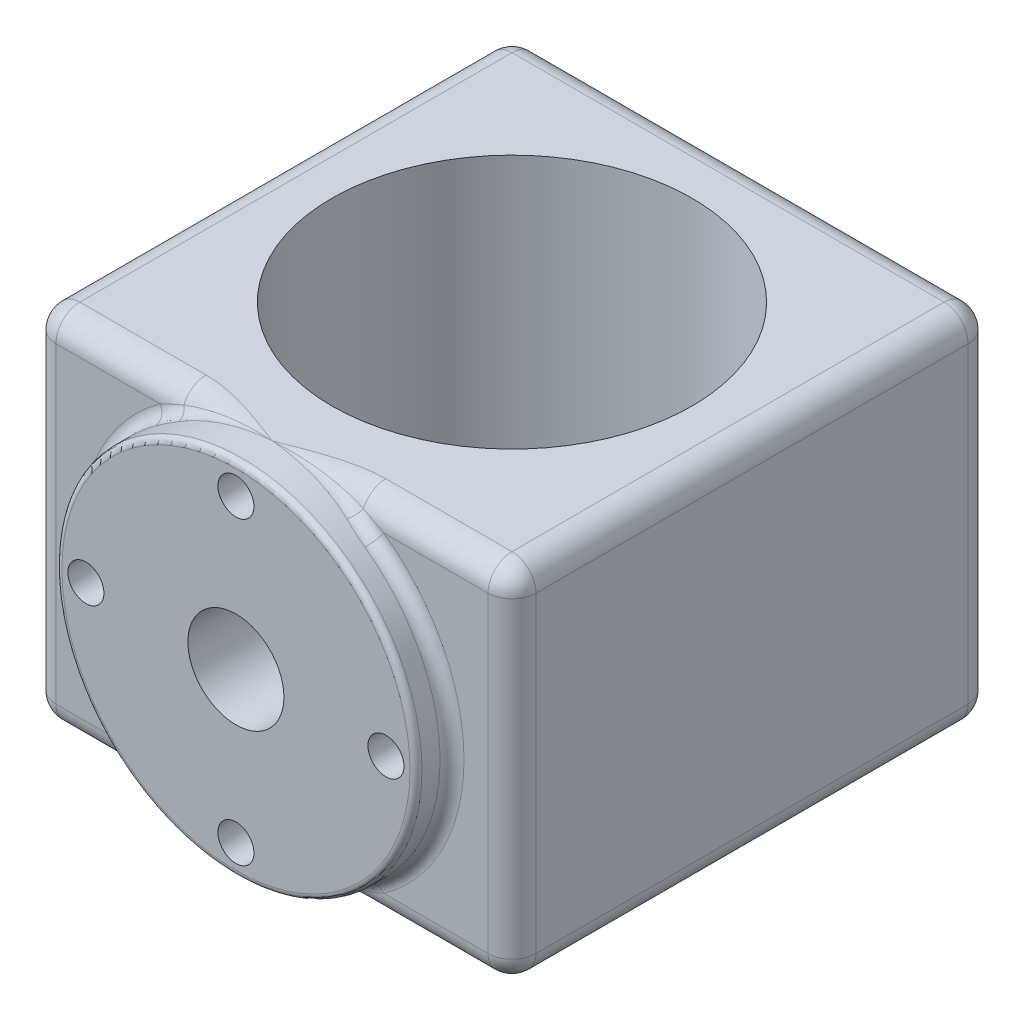
SolidWorks part; units mm, degrees
ref_plane "Front Plane" through (0, 0, 0) normal (0, 0, 1) x (1, 0, 0)
ref_plane "Top Plane" through (0, 0, 0) normal (0, 1, 0) x (1, 0, 0)
ref_plane "Right Plane" through (0, 0, 0) normal (1, 0, 0) x (0, 0, -1)
sketch "Sketch2" plane through (0, 0, 0) normal (0, 0, 1) x (1, 0, 0)
  line L2 (0, 0) -> (-12.5, 0) construction
  circle A0 centre (-12.5, 0) radius 1.5
  circle A5 centre (0, 0) radius 15
  circle A6 centre (0, 12.5) radius 1.5
  circle A7 centre (12.5, 0) radius 1.5
  circle A8 centre (0, -12.5) radius 1.5
  dimension "D1" = 30
  dimension "D2" = 3
  dimension "D3" = 12.5
  dimension "D4" = 4
extrude "Boss-Extrude1" add sketch "Sketch2" along normal blind 3
sketch "Sketch3" plane through (0, 0, 0) normal (0, 0, -1) x (-1, 0, 0)
  line L1 (-20, -15) -> (20, -15)
  line L2 (-20, -15) -> (-20, 15)
  line L3 (-20, 15) -> (20, 15)
  line L4 (20, -15) -> (20, 15)
  line L5 (-20, -15) -> (20, 15) construction
  line L6 (-20, 15) -> (20, -15) construction
  point P0 (0, 0)
  dimension "D1" = 30
  dimension "D2" = 40
extrude "Boss-Extrude2" add sketch "Sketch3" along normal blind 40
sketch "Sketch4" plane through (0, 15, 0) normal (0, 1, 0) x (1, 0, 0)
  line L0 (0, 0) -> (0, 40) construction
  line L1 (-20, 40) -> (20, 40) construction
  circle A0 centre (0, 20) radius 15
  dimension "D1" = 30
extrude "Cut-Extrude1" cut sketch "Sketch4" against normal up to surface (30 mm away) up to face at (0, -15, -16)
fillet "Fillet1" radius 2 14 edges at (-10, -15, 0) (-10, 15, 0) (-20, 0, 0) (20, 0, -40) (0, 15, -40) (-20, 0, -40) (-20, 15, -20) (-20, -15, -20) (0, -15, -40) (20, -15, -20) (10, -15, 0) (10, 15, 0) (20, 0, 0) (20, 15, -20)
fillet "Fillet2" radius 0.5 1 edges at (15, 0, 3)
fillet "Fillet3" radius 1 6 edges at (3.873, -14.4914, 0) (-3.873, -14.4914, 0) (-15, 0, 0) (-3.873, 14.4914, 0) (3.873, 14.4914, 0) (15, 0, 0)
sketch "Sketch5" plane through (0, 0, 3) normal (0, 0, 1) x (1, 0, 0)
  circle A0 centre (0, -12.5) radius 1.5 construction
  circle A1 centre (12.5, 0) radius 1.5 construction
  circle A2 centre (0, 12.5) radius 1.5 construction
  circle A3 centre (-12.5, 0) radius 1.5 construction
  circle A4 centre (0, -12.5) radius 1.5
  circle A5 centre (12.5, 0) radius 1.5
  circle A6 centre (0, 12.5) radius 1.5
  circle A7 centre (-12.5, 0) radius 1.5
  circle A8 centre (0, 0) radius 4
  dimension "D1" = 8
extrude "Cut-Extrude2" cut sketch "Sketch5" against normal blind 7
